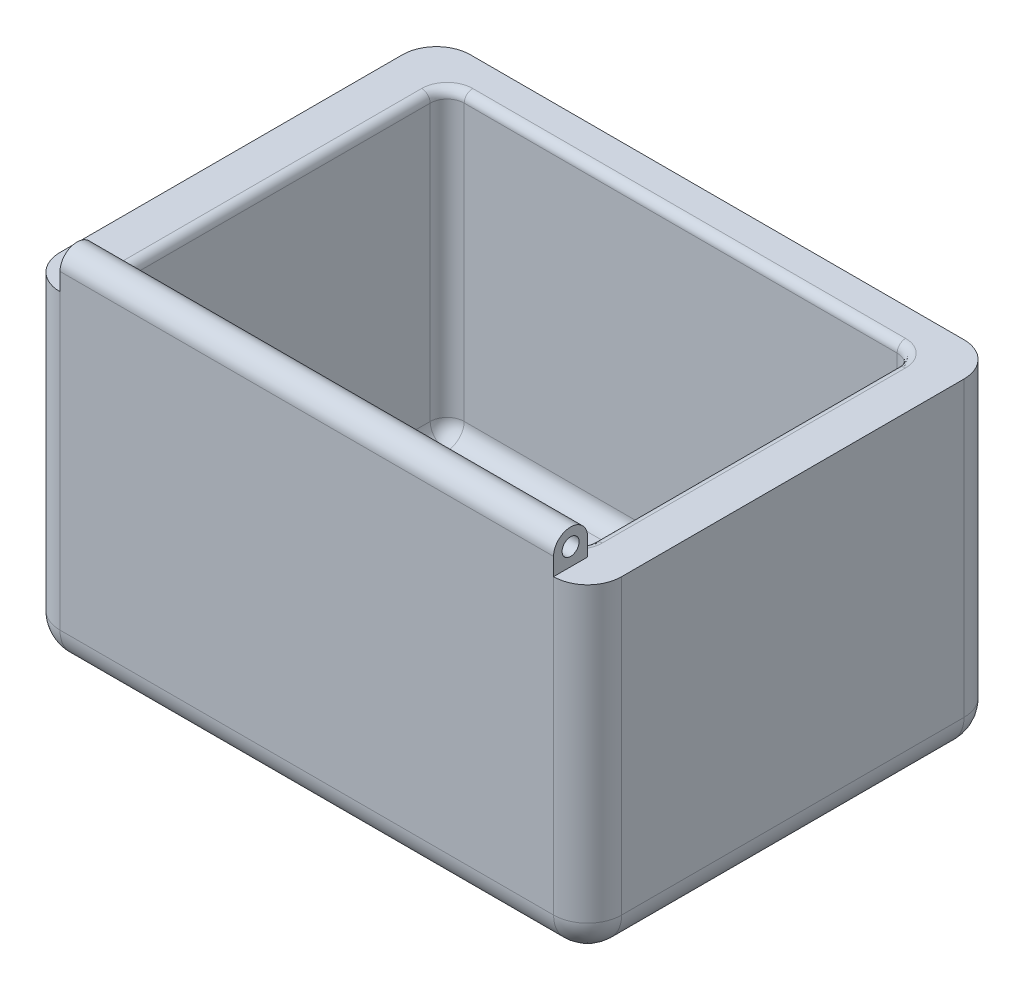
SolidWorks part; units mm, degrees
ref_plane "Front Plane" through (0, 0, 0) normal (0, 0, 1) x (1, 0, 0)
ref_plane "Top Plane" through (0, 0, 0) normal (0, 1, 0) x (1, 0, 0)
ref_plane "Right Plane" through (0, 0, 0) normal (1, 0, 0) x (0, 0, -1)
sketch "Sketch1" plane through (0, 0, 0) normal (0, 1, 0) x (1, 0, 0)
  line L1 (-165.1, -120.65) -> (165.1, -120.65)
  line L2 (-165.1, -120.65) -> (-165.1, 120.65)
  line L3 (-165.1, 120.65) -> (165.1, 120.65)
  line L4 (165.1, -120.65) -> (165.1, 120.65)
  line L5 (-165.1, -120.65) -> (165.1, 120.65) construction
  line L6 (-165.1, 120.65) -> (165.1, -120.65) construction
  point P0 (0, 0)
  dimension "D1" = 330.2
  dimension "D2" = 241.3
extrude "Boss-Extrude3" add sketch "Sketch1" along normal blind 192.3
sketch "Sketch4" plane through (0, 192.3, 0) normal (0, 1, 0) x (1, 0, 0)
  line L1 (-137.287, -99.187) -> (137.287, -99.187)
  line L2 (-137.287, -99.187) -> (-137.287, 99.187)
  line L3 (-137.287, 99.187) -> (137.287, 99.187)
  line L4 (137.287, -99.187) -> (137.287, 99.187)
  line L5 (-137.287, -99.187) -> (137.287, 99.187) construction
  line L6 (-137.287, 99.187) -> (137.287, -99.187) construction
  point P0 (0, 0)
  dimension "D1" = 274.574
  dimension "D2" = 198.374
extrude "Cut-Extrude1" cut sketch "Sketch4" against normal blind 176.276 draft 0.256
fillet "Fillet1" radius 20 7 edges at (165.1, 96.15, -120.65) (165.1, 96.15, 120.65) (0, 0, 120.65) (-165.1, 96.15, 120.65) (-165.1, 0, 0) (-165.1, 96.15, -120.65) (0, 0, -120.65)
fillet "Fillet2" radius 20 3 edges at (159.2421, 5.8579, 114.7921) (159.2421, 5.8579, -114.7921) (165.1, 0, 0)
fillet "Fillet3" radius 10 8 edges at (136.8932, 104.162, -98.7932) (-136.8932, 104.162, -98.7932) (0, 16.024, -98.3994) (136.4994, 16.024, 0) (136.8932, 104.162, 98.7932) (0, 16.024, 98.3994) (-136.4994, 16.024, 0) (-136.8932, 104.162, 98.7932)
fillet "Fillet4" radius 5 8 edges at (-134.3581, 192.3, 96.2581) (-137.287, 192.3, 0) (-134.3581, 192.3, -96.2581) (0, 192.3, -99.187) (134.3581, 192.3, -96.2581) (137.287, 192.3, 0) (134.3581, 192.3, 96.2581) (0, 192.3, 99.187)
ref_plane "Plane1" through (145.1, 0, 0) normal (1, 0, 0) x (0, 1, 0)
sketch "Sketch5" plane through (145.1, 0, 0) normal (1, 0, 0) x (0, 1, 0)
  line L0 (192.3, 100.65) -> (20, 100.65) construction
  line L1 (202.6192, 120.65) -> (192.3, 120.65)
  line L2 (202.6192, 100.65) -> (192.3, 100.65)
  line L3 (192.3, 120.65) -> (192.3, 100.65)
  arc A0 (202.6192, 100.65) -> (202.6192, 120.65) centre (202.6192, 110.65) ccw
  circle A1 centre (202.6192, 110.65) radius 5
  dimension "D1" = 20
  dimension "D2" = 10
  dimension "D3" = 10
extrude "Boss-Extrude4" add sketch "Sketch5" against normal blind 290.2
